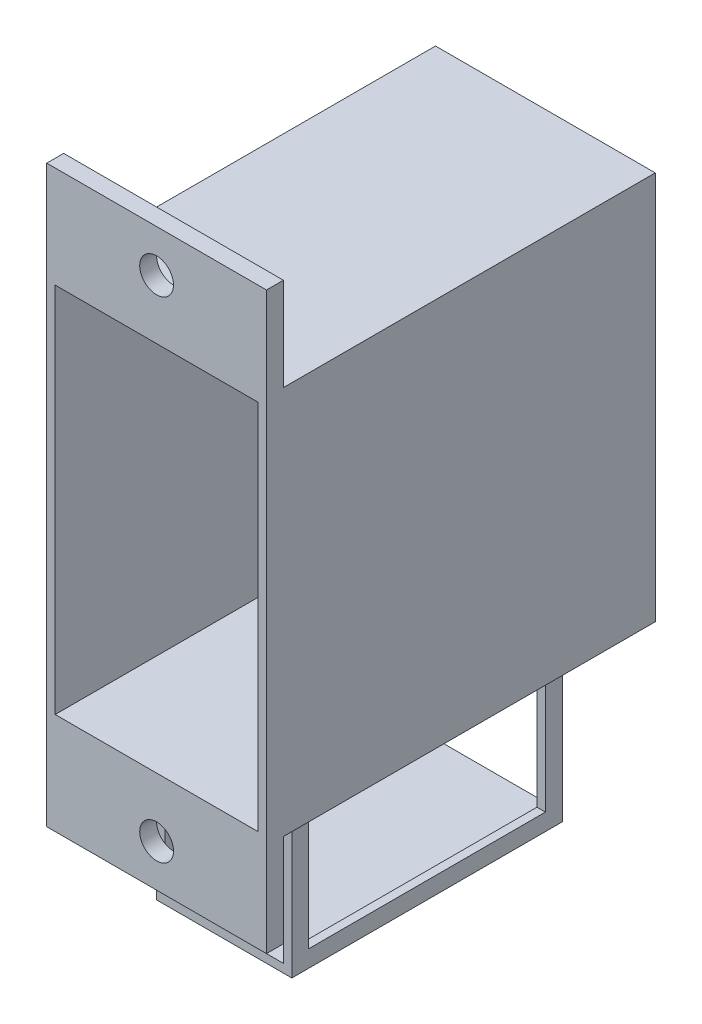
SolidWorks part; units mm, degrees
ref_plane "Front Plane" through (0, 0, 0) normal (0, 0, 1) x (1, 0, 0)
ref_plane "Top Plane" through (0, 0, 0) normal (0, 1, 0) x (1, 0, 0)
ref_plane "Right Plane" through (0, 0, 0) normal (1, 0, 0) x (0, 0, -1)
sketch "Sketch1" plane through (0, 0, 0) normal (0, 0, 1) x (1, 0, 0)
  line L1 (-6.5, 11.5) -> (6.5, 11.5)
  line L2 (-6.5, 11.5) -> (-6.5, -11.5)
  line L3 (-6.5, -11.5) -> (6.5, -11.5)
  line L4 (6.5, 11.5) -> (6.5, -11.5)
  line L5 (-6.5, 11.5) -> (6.5, -11.5) construction
  line L6 (-6.5, -11.5) -> (6.5, 11.5) construction
  line L7 (-6, 11) -> (6, 11)
  line L8 (-6, 11) -> (-6, -11)
  line L9 (-6, -11) -> (6, -11)
  line L10 (6, 11) -> (6, -11)
  line L11 (-6, 11) -> (6, -11) construction
  line L12 (-6, -11) -> (6, 11) construction
  point P0 (0, 0)
  point P6 (0, 0)
  dimension "D1" = 22
  dimension "D2" = 12
  dimension "D3" = 13
  dimension "D4" = 23
extrude "Boss-Extrude1" add sketch "Sketch1" along normal blind 23 contours L2 L3 L4 L1
extrude "Cut-Extrude1" cut sketch "Sketch1<3>" along normal up to next contours L7 L10 L9 L8
sketch "Sketch1<3>" plane through (0, 0, 0) normal (0, 0, 1) x (1, 0, 0) same geometry as "Sketch1"
ref_plane "Plane1" through (0, 0, 23) normal (0, 0, 1) x (1, 0, 0)
sketch "Sketch2" plane through (0, 0, 23) normal (0, 0, 1) x (1, 0, 0)
  line L0 (-6.5, 11.5) -> (-6.5, 17)
  line L1 (-6.5, 17) -> (6.5, 17)
  line L2 (6.5, 17) -> (6.5, 11.5)
  line L3 (6.5, 11.5) -> (-6.5, 11.5)
  line L4 (7.15, 0) -> (-7.15, 0) construction
  line L5 (6.5, -17) -> (6.5, -11.5)
  line L6 (-6.5, -17) -> (6.5, -17)
  line L7 (-6.5, -11.5) -> (-6.5, -17)
  line L8 (6.5, -11.5) -> (-6.5, -11.5)
  circle A0 centre (0, 14.5) radius 1
  circle A1 centre (0, -14.5) radius 1
  dimension "D3" = 2
  dimension "D1" = 5.5
  dimension "D2" = 3
extrude "Boss-Extrude2" add sketch "Sketch2" against normal blind 1
ref_plane "Plane3" through (0, -11.5, 0) normal (0, -1, 0) x (-1, 0, 0)
sketch "Sketch4" plane through (0, -11.5, 0) normal (0, -1, 0) x (-1, 0, 0)
  line L0 (6.5, -11) -> (-6.5, -11) construction
  line L1 (6.5, -22) -> (6.5, 0) construction
  line L2 (-6.5, -22) -> (-6.5, 0) construction
  line L3 (0, 0) -> (0, -23) construction
  line L4 (6.5, 0) -> (-6.5, 0) construction
  line L5 (-7.15, -23) -> (7.15, -23) construction
  line L7 (4, -19) -> (-4, -19)
  line L8 (4, -19) -> (4, -3)
  line L9 (4, -3) -> (-4, -3)
  line L10 (-4, -19) -> (-4, -3)
  line L11 (4, -19) -> (-4, -3) construction
  line L12 (4, -3) -> (-4, -19) construction
  point P12 (0, -11)
  dimension "D1" = 16
  dimension "D2" = 8
extrude "Boss-Extrude3" add sketch "Sketch4" along normal blind 10
ref_plane "Plane4" through (4, 0, 0) normal (1, 0, 0) x (0, 0, -1)
sketch "Sketch5" plane through (4, 0, 0) normal (1, 0, 0) x (0, 0, -1)
  line L0 (-11, -21.5) -> (-11, -11.5) construction
  line L1 (-3, -21.5) -> (-19, -21.5) construction
  line L2 (-3, -11.5) -> (-19, -11.5) construction
  line L3 (-19, -16.5) -> (-3, -16.5) construction
  line L4 (-19, -21.5) -> (-19, -11.5) construction
  line L5 (-3, -21.5) -> (-3, -11.5) construction
  line L7 (-18, -20.5) -> (-4, -20.5)
  line L8 (-18, -20.5) -> (-18, -12.5)
  line L9 (-18, -12.5) -> (-4, -12.5)
  line L10 (-4, -20.5) -> (-4, -12.5)
  line L11 (-18, -20.5) -> (-4, -12.5) construction
  line L12 (-18, -12.5) -> (-4, -20.5) construction
  point P12 (-11, -16.5)
  dimension "D1" = 14
  dimension "D2" = 8
extrude "Cut-Extrude2" cut sketch "Sketch5" against normal up to next
ref_plane "Plane5" through (0, 0, 3) normal (0, 0, -1) x (-1, 0, 0)
ref_plane "Plane6" through (0, 0, 3) normal (0, 0, -1) x (-1, 0, 0)
sketch "Sketch6" plane through (0, 0, 3) normal (0, 0, -1) x (-1, 0, 0)
  line L0 (0, -21.5) -> (0, -11.5) construction
  line L1 (4, -21.5) -> (-4, -21.5) construction
  line L2 (6.5, -11.5) -> (-6.5, -11.5) construction
  line L3 (4, -16.5) -> (-4, -16.5) construction
  line L4 (4, -21.5) -> (4, -11.5) construction
  line L5 (-4, 5.5) -> (-4, -5.5) construction
  line L7 (-3.5, -12) -> (3.5, -12)
  line L8 (-3.5, -12) -> (-3.5, -21)
  line L9 (-3.5, -21) -> (3.5, -21)
  line L10 (3.5, -12) -> (3.5, -21)
  line L11 (-3.5, -12) -> (3.5, -21) construction
  line L12 (-3.5, -21) -> (3.5, -12) construction
  point P12 (0, -16.5)
  dimension "D1" = 9
  dimension "D2" = 7
extrude "Cut-Extrude3" cut sketch "Sketch6" against normal up to next
ref_plane "Plane7" through (0, -21.5, 0) normal (0, -1, 0) x (-1, 0, 0)
sketch "Sketch7" plane through (0, -21.5, 0) normal (0, -1, 0) x (-1, 0, 0)
  line L0 (4, -11) -> (-4, -11) construction
  line L1 (4, -19) -> (4, -3) construction
  line L2 (-4, -3) -> (-4, -19) construction
  line L3 (0, -19) -> (0, -3) construction
  line L4 (-4, -19) -> (4, -19) construction
  line L5 (4.4, -3) -> (-4.4, -3) construction
  circle A0 centre (0, -11) radius 1.5 construction
  dimension "D1" = 3
